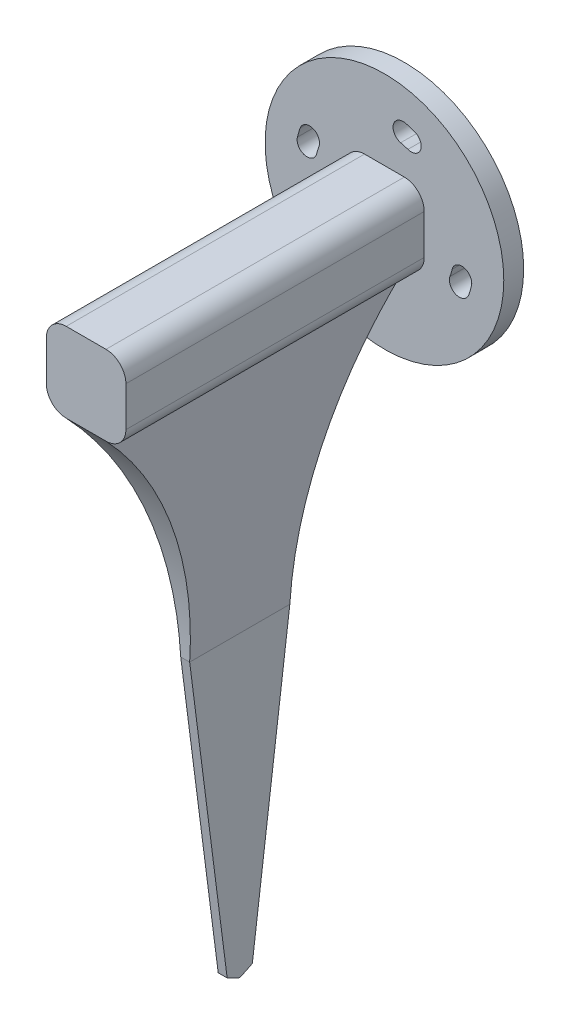
SolidWorks part; units mm, degrees
ref_plane "Plan de face" through (0, 0, 0) normal (0, 0, 1) x (1, 0, 0)
ref_plane "Plan de dessus" through (0, 0, 0) normal (0, 1, 0) x (1, 0, 0)
ref_plane "Plan de droite" through (0, 0, 0) normal (1, 0, 0) x (0, 0, -1)
sketch "Esquisse1" plane through (0, 0, 0) normal (0, 0, 1) x (1, 0, 0)
  circle A0 centre (0, 0) radius 12
  circle A2 centre (0, 0) radius 8
  arc A3 (-7.779, 1.8674) -> (-7.5319, 2.6964) centre (0, 0) cw construction
  arc A8 (-8.4734, 3.0334) -> (-8.7514, 2.1008) centre (0, 0) ccw
  arc A13 (-6.5904, 2.3593) -> (-6.8066, 1.634) centre (0, 0) ccw
  arc A14 (-6.5904, 2.3593) -> (-8.4734, 3.0334) centre (-7.5319, 2.6964) ccw
  arc A15 (-8.7514, 2.1008) -> (-6.8066, 1.634) centre (-7.779, 1.8674) ccw
  arc A16 (1.8674, 7.779) -> (2.6964, 7.5319) centre (0, 0) cw construction
  arc A17 (3.0334, 8.4734) -> (2.1008, 8.7514) centre (0, 0) ccw
  arc A18 (2.3593, 6.5904) -> (1.634, 6.8066) centre (0, 0) ccw
  arc A19 (2.3593, 6.5904) -> (3.0334, 8.4734) centre (2.6964, 7.5319) ccw
  arc A20 (2.1008, 8.7514) -> (1.634, 6.8066) centre (1.8674, 7.779) ccw
  arc A21 (7.779, -1.8674) -> (7.5319, -2.6964) centre (0, 0) cw construction
  arc A22 (8.4734, -3.0334) -> (8.7514, -2.1008) centre (0, 0) ccw
  arc A23 (6.5904, -2.3593) -> (6.8066, -1.634) centre (0, 0) ccw
  arc A24 (6.5904, -2.3593) -> (8.4734, -3.0334) centre (7.5319, -2.6964) ccw
  arc A25 (8.7514, -2.1008) -> (6.8066, -1.634) centre (7.779, -1.8674) ccw
  arc A26 (-1.8674, -7.779) -> (-2.6964, -7.5319) centre (0, 0) cw construction
  arc A27 (-3.0334, -8.4734) -> (-2.1008, -8.7514) centre (0, 0) ccw
  arc A28 (-2.3593, -6.5904) -> (-1.634, -6.8066) centre (0, 0) ccw
  arc A29 (-2.3593, -6.5904) -> (-3.0334, -8.4734) centre (-2.6964, -7.5319) ccw
  arc A30 (-2.1008, -8.7514) -> (-1.634, -6.8066) centre (-1.8674, -7.779) ccw
  point P7 (-7.6667, 2.2852)
  point P17 (2.2852, 7.6667)
  point P24 (7.6667, -2.2852)
  point P31 (-2.2852, -7.6667)
  point P36 (0, 0)
  dimension "D1" = 24
  dimension "D2" = 1
  dimension "D3" = 16
  dimension "D4" = 4
extrude "Boss.-Extru.1" add sketch "Esquisse1" along normal blind 2 contours A0 A19 A2 A15 | A19 A2 A15 region at (-11.6606, 0, 0) region at (0, 0, 0)
sketch "Esquisse2" plane through (0, 0, 2) normal (0, 0, 1) x (1, 0, 0)
  line L1 (-2, 4) -> (2, 4)
  line L2 (-4, 2) -> (-4, -2)
  line L3 (-2, -4) -> (2, -4)
  line L4 (4, 2) -> (4, -2)
  line L5 (-4, 4) -> (4, -4) construction
  line L6 (-4, -4) -> (4, 4) construction
  arc A1 (-4, -2) -> (-2, -4) centre (-2, -2) ccw
  arc A2 (2, -4) -> (4, -2) centre (2, -2) ccw
  arc A3 (2, 4) -> (4, 2) centre (2, 2) cw
  arc A4 (-2, 4) -> (-4, 2) centre (-2, 2) ccw
  point P0 (0, 0)
  dimension "D1" = 8
  dimension "D3" = 2
  dimension "D2" = 8
extrude "Boss.-Extru.2" add sketch "Esquisse2" along normal blind 30
sketch "Esquisse3" plane through (0, 0, 0) normal (1, 0, 0) x (0, 0, -1)
  line L0 (-4, -39) -> (-30, -39) construction
  line L5 (-32, -4) -> (-2, -4) construction
  line L6 (-32, -4) -> (-2, -4)
  line L7 (-30, -29) -> (-4, -29)
  line L8 (-30, -29) -> (-30, -59)
  line L9 (-30, -59) -> (-4, -59)
  line L10 (-4, -29) -> (-4, -59)
  line L11 (-30, -29) -> (-4, -59) construction
  line L12 (-30, -59) -> (-4, -29) construction
  line L13 (-17, -29) -> (-17, -28) construction
  line L14 (-17, -59) -> (-17, -55.98) construction
  line L15 (-18.2666, -58.3879) -> (-22.0362, -29)
  line L16 (-15.7334, -58.3879) -> (-11.9638, -29)
  arc A4 (-4, -39) -> (-11.9638, -29) centre (-17, -41.1818) ccw
  arc A5 (-22.0362, -29) -> (-30, -39) centre (-17, -41.1818) ccw
  arc A6 (-30, -39) -> (-17, -59) centre (-8.1154, -39) ccw
  arc A7 (-4, -39) -> (-17, -59) centre (-25.8846, -39) cw
  point P0 (-17, -44)
  point P5 (-17, -29)
  point P8 (-17, -4)
  point P15 (-17, -59)
  dimension "D5" = 1
  dimension "D1" = 25
  dimension "D2" = 30
  dimension "D3" = 26
  dimension "D4" = 10
extrude "Boss.-Extru.3" add sketch "Esquisse3" along normal mid plane 0.9 separate body contours A7 A4 L7 A5 A6 region at (0, -40.8409, 17)
sketch "Esquisse4" plane through (0, -4, 0) normal (0, -1, 0) x (1, 0, 0)
  line L0 (2, 32) -> (2, 2) construction
  line L1 (-2, 32) -> (2, 32)
  line L2 (-2, 32) -> (-2, 27.05)
  line L3 (-2, 27.05) -> (2, 27.05)
  line L4 (2, 32) -> (2, 27.05)
  dimension "D1" = 4.95
loft "Lissage1" add section face at (0, -29, 17) section face at (0, -4, 17) connector at (0.45, -29, 11.9638) connector at (2, -4, 2)
sketch "Esquisse5" plane through (4, 0, 0) normal (-1, 0, 0) x (0, 0, 1)
  line L3 (11.9638, -29) -> (11.9638, -13.8858) construction
  line L4 (22.0362, -29) -> (32, -4) construction
  line L5 (11.9638, -29) -> (2, -4) construction
  line L6 (22.0362, -29) -> (32, -4)
  line L7 (11.9638, -29) -> (2, -4)
  circle A2 centre (58.3818, -29) radius 36.3455
  circle A3 centre (-24.3818, -29) radius 36.3455
extrude "Enlèv. mat.-Extru.1" cut sketch "Esquisse5" along normal up to surface (4.45 mm away) contours A2 L6 | A3 L7 region at (4, -16.1163, 26.0555) region at (4, -16.1163, 7.9445) up to face at (-0.8375, -22.75, 18.2591)
